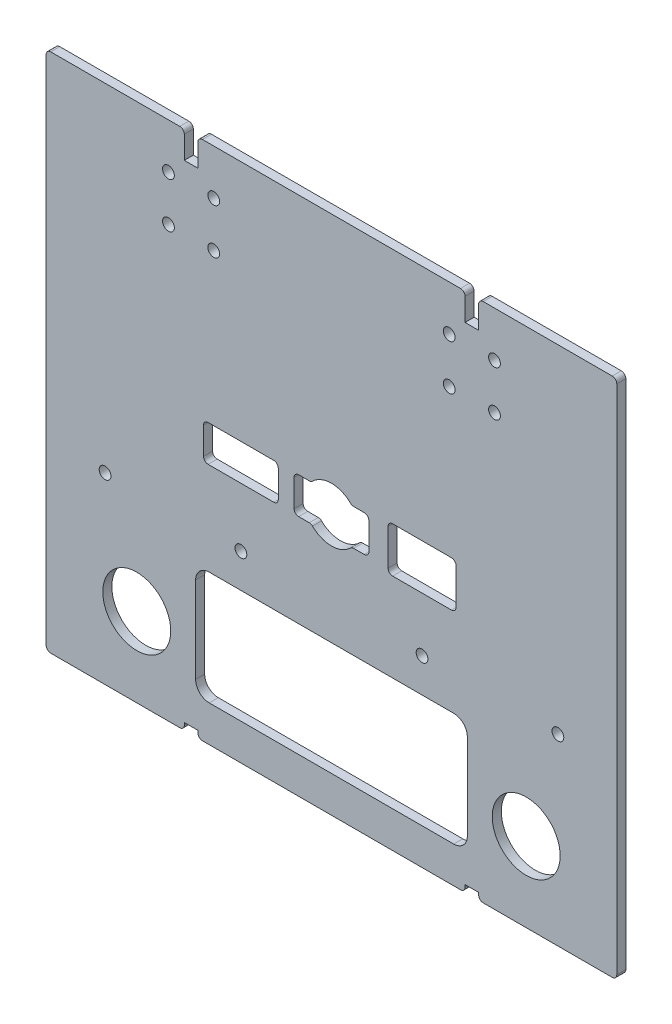
SolidWorks part; units mm, degrees
ref_plane "Front Plane" through (0, 0, 0) normal (0, 0, 1) x (1, 0, 0)
ref_plane "Top Plane" through (0, 0, 0) normal (0, 1, 0) x (1, 0, 0)
ref_plane "Right Plane" through (0, 0, 0) normal (1, 0, 0) x (0, 0, -1)
sketch "Sketch1" plane through (0, 0, 0) normal (0, 0, 1) x (1, 0, 0)
  line L1 (-63, 57.5) -> (63, 57.5)
  line L2 (-63, 57.5) -> (-63, -57.5)
  line L3 (-63, -57.5) -> (63, -57.5)
  line L4 (63, 57.5) -> (63, -57.5)
  line L5 (-63, 57.5) -> (63, -57.5) construction
  line L6 (-63, -57.5) -> (63, 57.5) construction
  point P0 (0, 0)
  dimension "D1" = 126
  dimension "D2" = 115
extrude "Boss-Extrude1" add sketch "Sketch1" along normal blind 2
sketch "Sketch2" plane through (0, 0, 2) normal (0, 0, 1) x (1, 0, 0)
  line L0 (-43, -40) -> (43, -40) construction
  line L1 (0, 0) -> (0, -40) construction
  line L3 (-30, -24.5) -> (30, -24.5)
  line L4 (-30, -24.5) -> (-30, -49.5)
  line L5 (-30, -49.5) -> (30, -49.5)
  line L6 (30, -24.5) -> (30, -49.5)
  line L7 (-30, -24.5) -> (30, -49.5) construction
  line L8 (-30, -49.5) -> (30, -24.5) construction
  line L9 (-63, -57.5) -> (63, -57.5) construction
  circle A0 centre (-43, -40) radius 7.5
  circle A1 centre (43, -40) radius 7.5
  point P7 (0, -37)
  dimension "D1" = 15
  dimension "D2" = 86
  dimension "D3" = 40
  dimension "D4" = 60
  dimension "D5" = 25
  dimension "D6" = 8
extrude "Cut-Extrude1" cut sketch "Sketch2" against normal blind 2 contours A0 | A1 | L6 L3 L4 L5 region at (0, -37, 2) region at (-43, -40, 2) region at (43, -40, 2)
fillet "Fillet1" radius 3 4 edges at (30, -49.5, 1) (-30, -49.5, 1) (30, -24.5, 1) (-30, -24.5, 1)
sketch "Sketch3" plane through (0, 0, 2) normal (0, 0, 1) x (1, 0, 0)
  line L0 (-30, 57.5) -> (-30, 0) construction
  line L1 (63, 57.5) -> (-63, 57.5) construction
  line L2 (0, 0) -> (0, 57.5) construction
  circle A0 centre (-26, 47.5) radius 1.3
  circle A1 centre (-36, 47.5) radius 1.3
  circle A2 centre (36, 47.5) radius 1.3
  circle A3 centre (26, 47.5) radius 1.3
  circle A4 centre (-26, 37.5) radius 1.3
  circle A5 centre (-36, 37.5) radius 1.3
  circle A6 centre (36, 37.5) radius 1.3
  circle A7 centre (26, 37.5) radius 1.3
  dimension "D5" = 2.6
  dimension "D1" = 30
  dimension "D2" = 4
  dimension "D3" = 6
  dimension "D4" = 10
  dimension "D7" = 10
  dimension "D6" = 2
extrude "Cut-Extrude2" cut sketch "Sketch3" against normal blind 4
sketch "Sketch4" plane through (0, 0, 0) normal (0, 0, -1) x (-1, 0, 0)
  line L0 (-63, 57.5) -> (63, 57.5) construction
  line L1 (-36, 47.5) -> (36, 47.5) construction
  line L2 (-36, 47.5) -> (-36, 57.5) construction
  line L3 (-36, 57.5) -> (36, 57.5) construction
  line L4 (36, 47.5) -> (36, 57.5) construction
  line L5 (-26, 47.5) -> (-26, 57.5) construction
  line L6 (26, 47.5) -> (26, 57.5) construction
  line L7 (-36, 57.5) -> (-26, 47.5) construction
  line L8 (-26, 57.5) -> (-36, 47.5) construction
  line L9 (26, 57.5) -> (36, 47.5) construction
  line L10 (26, 47.5) -> (36, 57.5) construction
  line L11 (-31, 52.5) -> (-31, 57.5) construction
  line L12 (31, 52.5) -> (31, 57.5) construction
  line L13 (63, -57.5) -> (-63, -57.5) construction
  line L14 (-32.5, 57.5) -> (-29.5, 57.5)
  line L15 (-32.5, 57.5) -> (-32.5, 51.5)
  line L16 (-32.5, 51.5) -> (-29.5, 51.5)
  line L17 (-29.5, 57.5) -> (-29.5, 51.5)
  line L18 (29.5, 57.5) -> (32.5, 57.5)
  line L19 (29.5, 57.5) -> (29.5, 51.5)
  line L20 (29.5, 51.5) -> (32.5, 51.5)
  line L21 (32.5, 57.5) -> (32.5, 51.5)
  line L22 (32.5, -57.5) -> (29.5, -57.5)
  line L23 (32.5, -57.5) -> (32.5, -56)
  line L24 (32.5, -56) -> (29.5, -56)
  line L25 (29.5, -57.5) -> (29.5, -56)
  line L27 (-32.5, -57.5) -> (-29.5, -57.5)
  line L28 (-32.5, -57.5) -> (-32.5, -56)
  line L29 (-32.5, -56) -> (-29.5, -56)
  line L30 (-29.5, -57.5) -> (-29.5, -56)
  dimension "D1" = 1
  dimension "D2" = 1.5
  dimension "D3" = 1.5
  dimension "D4" = 1
  dimension "D5" = 1.5
  dimension "D6" = 1.5
  dimension "D7" = 1.5
extrude "Cut-Extrude3" cut sketch "Sketch4" against normal blind 10
fillet "Fillet2" radius 1 12 edges at (-32.5, 57.5, 1) (-29.5, 57.5, 1) (29.5, 57.5, 1) (32.5, 57.5, 1) (-63, 57.5, 1) (63, 57.5, 1) (-63, -57.5, 1) (63, -57.5, 1) (32.5, -57.5, 1) (29.5, -57.5, 1) (-29.5, -57.5, 1) (-32.5, -57.5, 1)
sketch "Sketch6" plane through (0, 0, 2) normal (0, 0, 1) x (1, 0, 0)
  line L1 (-8.25, 4) -> (8.25, 4)
  line L2 (-8.25, 4) -> (-8.25, -4)
  line L3 (-8.25, -4) -> (8.25, -4)
  line L4 (8.25, 4) -> (8.25, -4)
  line L5 (-8.25, 4) -> (8.25, -4) construction
  line L6 (-8.25, -4) -> (8.25, 4) construction
  line L7 (12.5, 5) -> (27.5, 5)
  line L8 (12.5, 5) -> (12.5, -5)
  line L9 (12.5, -5) -> (27.5, -5)
  line L10 (27.5, 5) -> (27.5, -5)
  line L11 (12.5, 5) -> (27.5, -5) construction
  line L12 (12.5, -5) -> (27.5, 5) construction
  line L17 (-28.25, 4) -> (-11.75, 4)
  line L18 (-28.25, 4) -> (-28.25, -4)
  line L19 (-28.25, -4) -> (-11.75, -4)
  line L20 (-11.75, 4) -> (-11.75, -4)
  line L21 (-28.25, 4) -> (-11.75, -4) construction
  line L22 (-28.25, -4) -> (-11.75, 4) construction
  circle A0 centre (0, 0) radius 6
  point P0 (0, 0)
  point P7 (20, 0)
  point P21 (-20, 0)
  dimension "D3" = 12
  dimension "D1" = 16.5
  dimension "D2" = 8
  dimension "D4" = 10
  dimension "D5" = 15
  dimension "D6" = 20
  dimension "D8" = 20
extrude "Cut-Extrude5" cut sketch "Sketch6" against normal blind 10 contours L10 L7 L8 L9 | L1 A0 L3 | A0 L3 L4 L1 | L1 A0 | A0 L1 L2 L3 | L3 A0 | L20 L17 L18 L19 region at (-6.8487, 0, 2) region at (0, 4.8127, 2) region at (0, 0, 2) region at (6.8487, 0, 2) region at (0, -4.8127, 2) region at (20, 0, 2) region at (-20, 0, 2)
fillet "Fillet3" radius 1 16 edges at (12.5, 5, 1) (27.5, 5, 1) (27.5, -5, 1) (12.5, -5, 1) (-8.25, -4, 1) (-4.4721, -4, 1) (4.4721, -4, 1) (8.25, -4, 1) (8.25, 4, 1) (4.4721, 4, 1) (-4.4721, 4, 1) (-8.25, 4, 1) (-11.75, 4, 1) (-11.75, -4, 1) (-28.25, -4, 1) (-28.25, 4, 1)
sketch "Sketch7" plane through (0, 0, 0) normal (0, 0, -1) x (-1, 0, 0)
  line L0 (-63, -17) -> (63, -17) construction
  line L1 (-63, -56.5) -> (-63, 56.5) construction
  line L2 (63, 56.5) -> (63, -56.5) construction
  circle A0 centre (-50, -17) radius 1.3
  circle A1 centre (-20, -17) radius 1.3
  circle A2 centre (20, -17) radius 1.3
  circle A3 centre (50, -17) radius 1.3
  dimension "D6" = 2.6
  dimension "D1" = 17
  dimension "D2" = 20
  dimension "D3" = 20
  dimension "D4" = 30
  dimension "D5" = 30
extrude "Cut-Extrude6" cut sketch "Sketch7" against normal blind 2.5
